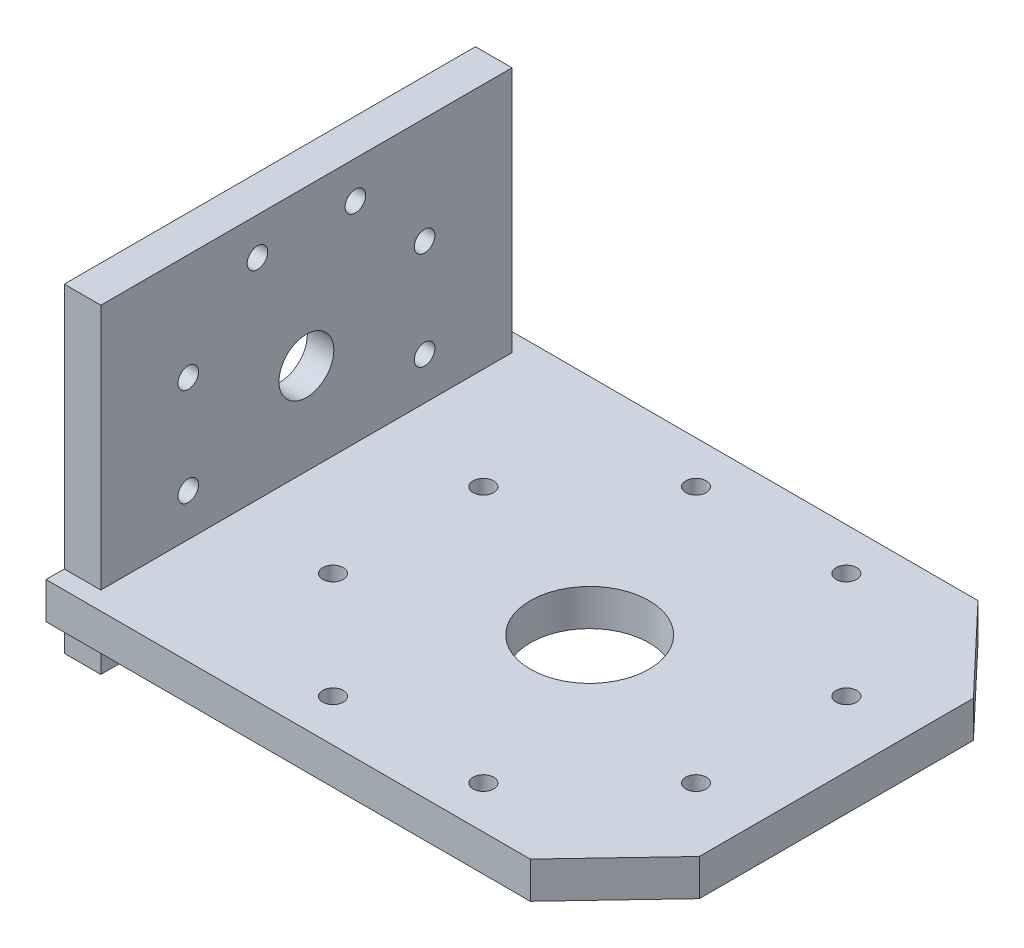
SolidWorks part; units mm, degrees
ref_plane "Front Plane" through (0, 0, 0) normal (0, 0, 1) x (1, 0, 0)
ref_plane "Top Plane" through (0, 0, 0) normal (0, 1, 0) x (1, 0, 0)
ref_plane "Right Plane" through (0, 0, 0) normal (1, 0, 0) x (0, 0, -1)
ref_plane "PL_Back_Plate_base" through (-70, 0, 0) normal (1, 0, 0) x (0, 0, -1)
sketch "SK_Back_Plate" plane through (-70, 0, 0) normal (1, 0, 0) x (0, 0, -1)
  line L0 (45, -36) -> (45, 34)
  line L1 (45, 34) -> (-45, 34)
  line L2 (-45, 34) -> (-45, -36)
  line L3 (-45, -36) -> (45, -36)
  circle A0 centre (25.8686, 10.7151) radius 2.25
  circle A1 centre (10.7151, 25.8686) radius 2.25
  circle A2 centre (-10.7151, 25.8686) radius 2.25
  circle A3 centre (-25.8686, 10.7151) radius 2.25
  circle A4 centre (-25.8686, -10.7151) radius 2.25
  circle A5 centre (-10.7151, -25.8686) radius 2.25
  circle A6 centre (10.7151, -25.8686) radius 2.25
  circle A7 centre (25.8686, -10.7151) radius 2.25
  circle A8 centre (0, 0) radius 6
  dimension "D9_SK_Back_Plate" = 4.5
  dimension "D12_SK_Back_Plate" = 4.5
  dimension "D15_SK_Back_Plate" = 4.5
  dimension "D18_SK_Back_Plate" = 4.5
  dimension "D21_SK_Back_Plate" = 4.5
  dimension "D24_SK_Back_Plate" = 4.5
  dimension "D27_SK_Back_Plate" = 4.5
  dimension "D30_SK_Back_Plate" = 4.5
  dimension "D33_SK_Back_Plate" = 12
  dimension "P1" = 45
  dimension "P2" = 36
  dimension "P3" = 45
  dimension "P4" = 34
  dimension "P5" = 45
  dimension "P6" = 34
  dimension "P7" = 45
  dimension "P8" = 36
  dimension "P10" = 25.8686
  dimension "P11" = 10.7151
  dimension "P13" = 10.7151
  dimension "P14" = 25.8686
  dimension "P16" = 10.7151
  dimension "P17" = 25.8686
  dimension "P19" = 25.8686
  dimension "P20" = 10.7151
  dimension "P22" = 25.8686
  dimension "P23" = 10.7151
  dimension "P25" = 10.7151
  dimension "P26" = 25.8686
  dimension "P28" = 10.7151
  dimension "P29" = 25.8686
  dimension "P31" = 25.8686
  dimension "P32" = 10.7151
extrude "Back_Plate" add sketch "SK_Back_Plate" along normal blind 8
ref_plane "PL_Roll_Pilot_Recess_base" through (-70, 0, 0) normal (1, 0, 0) x (0, 0, -1)
sketch "SK_Roll_Pilot_Recess" plane through (-70, 0, 0) normal (1, 0, 0) x (0, 0, -1)
  circle A0 centre (0, 0) radius 22.15
  dimension "D1_SK_Roll_Pilot_Recess" = 44.3
extrude "Roll_Pilot_Recess" cut sketch "SK_Roll_Pilot_Recess" along normal blind 2.2
ref_plane "PL_Medial_Plate_base" through (0, -28, 0) normal (0, 1, 0) x (1, 0, 0)
sketch "SK_Medial_Plate" plane through (0, -28, 0) normal (0, 1, 0) x (1, 0, 0)
  line L0 (-70, 49) -> (36, 49)
  line L1 (36, 49) -> (54, 30)
  line L2 (54, 30) -> (54, -30)
  line L3 (54, -30) -> (36, -49)
  line L4 (36, -49) -> (-70, -49)
  line L5 (-70, -49) -> (-70, 49)
  circle A0 centre (39.7268, 16.4554) radius 2.25
  circle A1 centre (16.4554, 39.7268) radius 2.25
  circle A2 centre (-16.4554, 39.7268) radius 2.25
  circle A3 centre (-39.7268, 16.4554) radius 2.25
  circle A4 centre (-39.7268, -16.4554) radius 2.25
  circle A5 centre (-16.4554, -39.7268) radius 2.25
  circle A6 centre (16.4554, -39.7268) radius 2.25
  circle A7 centre (39.7268, -16.4554) radius 2.25
  circle A8 centre (0, 0) radius 13
  dimension "D13_SK_Medial_Plate" = 4.5
  dimension "D16_SK_Medial_Plate" = 4.5
  dimension "D19_SK_Medial_Plate" = 4.5
  dimension "D22_SK_Medial_Plate" = 4.5
  dimension "D25_SK_Medial_Plate" = 4.5
  dimension "D28_SK_Medial_Plate" = 4.5
  dimension "D31_SK_Medial_Plate" = 4.5
  dimension "D34_SK_Medial_Plate" = 4.5
  dimension "D37_SK_Medial_Plate" = 26
  dimension "P1" = 70
  dimension "P2" = 49
  dimension "P3" = 36
  dimension "P4" = 49
  dimension "P5" = 54
  dimension "P6" = 30
  dimension "P7" = 54
  dimension "P8" = 30
  dimension "P9" = 36
  dimension "P10" = 49
  dimension "P11" = 70
  dimension "P12" = 49
  dimension "P14" = 39.7268
  dimension "P15" = 16.4554
  dimension "P17" = 16.4554
  dimension "P18" = 39.7268
  dimension "P20" = 16.4554
  dimension "P21" = 39.7268
  dimension "P23" = 39.7268
  dimension "P24" = 16.4554
  dimension "P26" = 39.7268
  dimension "P27" = 16.4554
  dimension "P29" = 16.4554
  dimension "P30" = 39.7268
  dimension "P32" = 16.4554
  dimension "P33" = 39.7268
  dimension "P35" = 39.7268
  dimension "P36" = 16.4554
extrude "Medial_Plate" add sketch "SK_Medial_Plate" along normal blind 8
equation "\"Roll_face_x\" = -70"
equation "\"Pitch_rear_y\" = -20"
